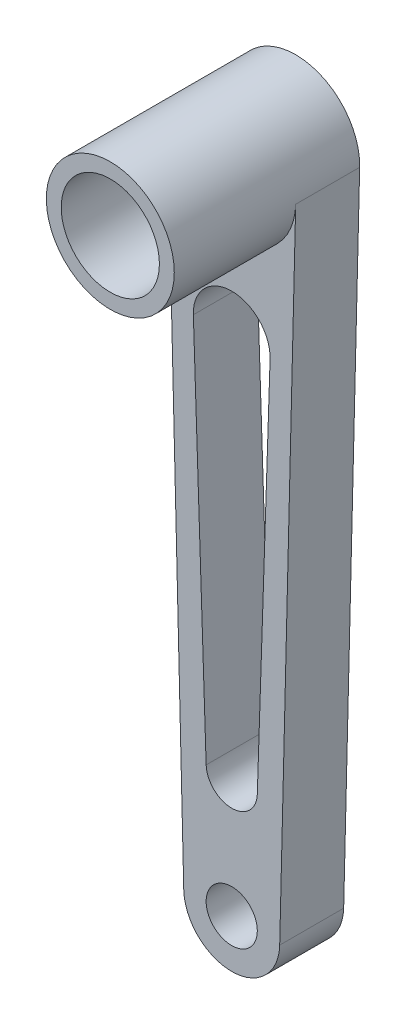
SolidWorks part; units mm, degrees
material "PEI"
ref_plane "Front Plane" through (0, 0, 0) normal (0, 0, 1) x (1, 0, 0)
ref_plane "Top Plane" through (0, 0, 0) normal (0, 1, 0) x (1, 0, 0)
ref_plane "Right Plane" through (0, 0, 0) normal (1, 0, 0) x (0, 0, -1)
sketch "Sketch1" plane through (0, 0, 0) normal (0, 0, 1) x (1, 0, 0)
  line L0 (-10.294, 11.8201) -> (-7.347, -107.9077)
  line L1 (0, -101.6) -> (0, 0) construction
  line L2 (7.347, -107.9067) -> (10.2653, 10.6574)
  line L3 (6.244, -15.7837) -> (3.867, -87.0546)
  line L4 (-6.2592, -15.3276) -> (-3.8401, -87.8596)
  circle A0 centre (0, 0) radius 10
  circle A1 centre (0, 0) radius 7.675
  circle A2 centre (0, -101.6) radius 7.5
  circle A3 centre (0, -101.6) radius 4
  circle A6 centre (0, -23) radius 6
  circle A7 centre (0, -83) radius 4
  dimension "D1" = 15.35
  dimension "D2" = 20
  dimension "D3" = 15
  dimension "D5" = 8
  dimension "D7" = 12
  dimension "D8" = 60
  dimension "D9" = 23
  dimension "D6" = 8
  dimension "D4" = 101.6
extrude "Boss-Extrude2" add sketch "Sketch1" along normal blind 10 contours L1 A2 L2 A0 | A2 L1 A0 L0 | A3 A2 region at (0, -11.0349, 0) region at (-0.0897, -94.3127, 0)
extrude "Boss-Extrude3" add sketch "Sketch1<6>" along normal blind 28.98 contours A0 A1 region at (-0.1196, 9.7164, 0)
sketch "Sketch1<6>" plane through (0, 0, 0) normal (0, 0, 1) x (1, 0, 0) same geometry as "Sketch1"
